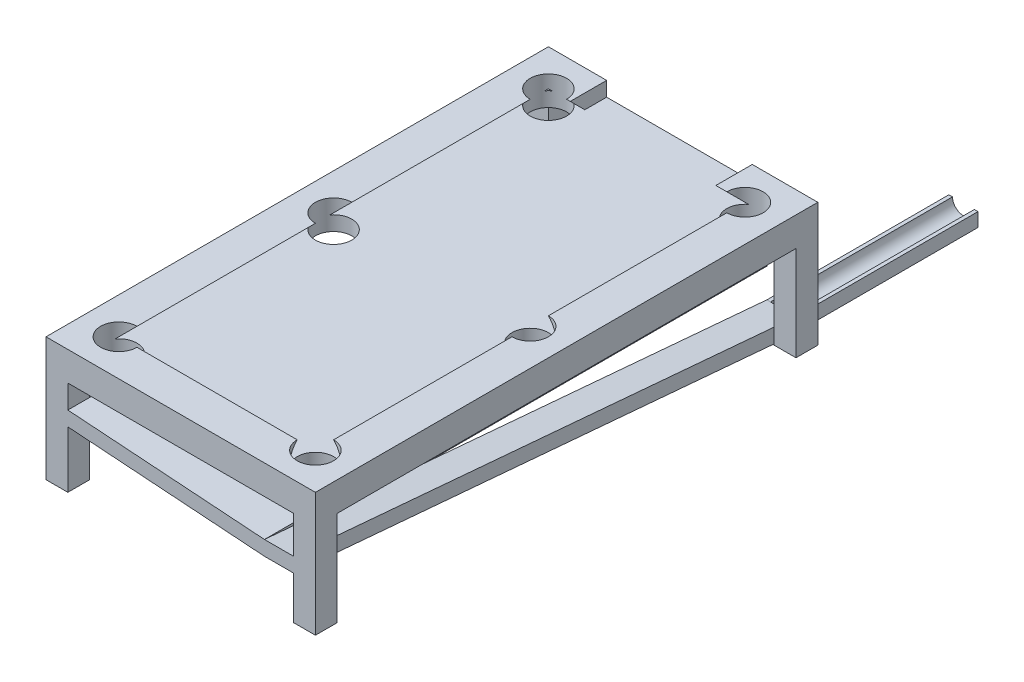
SolidWorks part; units mm, degrees
ref_plane "Front Plane" through (0, 0, 0) normal (0, 0, 1) x (1, 0, 0)
ref_plane "Top Plane" through (0, 0, 0) normal (0, 1, 0) x (1, 0, 0)
ref_plane "Right Plane" through (0, 0, 0) normal (1, 0, 0) x (0, 0, -1)
sketch "Sketch2" plane through (0, 0, 0) normal (0, 1, 0) x (1, 0, 0)
  line L1 (0, 0) -> (370, 0)
  line L2 (0, 0) -> (0, 690)
  line L3 (0, 690) -> (370, 690)
  line L4 (370, 0) -> (370, 690)
  line L5 (50, 50) -> (320, 50)
  line L6 (50, 50) -> (50, 640)
  line L7 (50, 640) -> (320, 640)
  line L8 (320, 50) -> (320, 640)
  dimension "D1" = 690
  dimension "D2" = 370
  dimension "D3" = 590
  dimension "D4" = 270
  dimension "D5" = 50
  dimension "D6" = 50
extrude "Boss-Extrude1" add sketch "Sketch2" along normal blind 20
chamfer "Chamfer1" distance 20 angle 45 4 edges at (185, 0, -640) (320, 0, -345) (185, 0, -50) (50, 0, -345)
ref_plane "Plane1" through (0, 0, -690) normal (0, 0, -1) x (-1, 0, 0)
sketch "Sketch10" plane through (0, 0, 0) normal (0, -1, 0) x (1, 0, 0)
  line L1 (0, 0) -> (370, 0)
  line L2 (0, 0) -> (0, -690)
  line L3 (0, -690) -> (370, -690)
  line L4 (370, 0) -> (370, -690)
extrude "Boss-Extrude6" add sketch "Sketch10" along normal blind 20
sketch "Sketch4" plane through (0, 20, 0) normal (0, 1, 0) x (1, 0, 0)
  line L0 (320, 640) -> (50, 640) construction
  line L1 (50, 640) -> (50, 50) construction
  line L2 (320, 50) -> (320, 640) construction
  circle A0 centre (320, 640) radius 25
  circle A1 centre (50, 640) radius 25
  circle A2 centre (50, 50) radius 25
  circle A3 centre (320, 50) radius 25
  circle A4 centre (320, 345) radius 25
  circle A5 centre (50, 345) radius 25
  line M11 (50, 50) -> (50, 640)
  line M12 (50, 640) -> (320, 640)
  line M13 (320, 640) -> (320, 50)
  line M14 (320, 50) -> (50, 50)
  dimension "D1" = 50
extrude "Cut-Extrude3" cut sketch "Sketch4" against normal through all contours A0 M12 M13 | A0 M13 M12 | A1 M11 M12 | A1 M12 M11 | A5 M11 | A5 M11 | A2 M14 M11 | A2 M11 M14 | A3 M13 M14 | A3 M14 M13 | A4 M13 | A4 M13 | A1 region at (323.5368, 20, -643.5368) region at (309.3897, 20, -629.3897) region at (46.4632, 20, -643.5368) region at (60.6103, 20, -629.3897) region at (309.3897, 20, -345) region at (330.6103, 20, -345) region at (39.3897, 20, -345) region at (60.6103, 20, -345) region at (309.3897, 20, -60.6103) region at (323.5368, 20, -46.4632) region at (46.4632, 20, -46.4632) region at (60.6103, 20, -60.6103)
sketch "Sketch11" plane through (0, -20, 0) normal (0, -1, 0) x (1, 0, 0)
  line L1 (0, 0) -> (30, 0)
  line L2 (0, 0) -> (0, -30)
  line L3 (0, -30) -> (30, -30)
  line L4 (30, 0) -> (30, -30)
  line L5 (370, 0) -> (340, 0)
  line L6 (370, 0) -> (370, -30)
  line L7 (370, -30) -> (340, -30)
  line L8 (340, 0) -> (340, -30)
  line L9 (0, -690) -> (30, -690)
  line L10 (0, -690) -> (0, -660)
  line L11 (0, -660) -> (30, -660)
  line L12 (30, -690) -> (30, -660)
  line L13 (370, -690) -> (340, -690)
  line L14 (370, -690) -> (370, -660)
  line L15 (370, -660) -> (340, -660)
  line L16 (340, -690) -> (340, -660)
  dimension "D1" = 30
extrude "Boss-Extrude7" add sketch "Sketch11" along normal blind 130
sketch "Sketch13" plane through (0, 20, 0) normal (0, 1, 0) x (1, 0, 0)
  line L0 (22, 690) -> (-22, 690) construction
  line L1 (80, 690) -> (280, 690)
  line L2 (80, 690) -> (80, 640)
  line L3 (80, 640) -> (280, 640)
  line L4 (280, 690) -> (280, 640)
  line L5 (295, 640) -> (75, 640) construction
  line L6 (0, 690) -> (0, 0) construction
  dimension "D1" = 200
  dimension "D2" = 80
extrude "Cut-Extrude4" cut sketch "Sketch13" against normal blind 20
sketch "Sketch14" plane through (0, 0, 0) normal (0, 0, 1) x (1, 0, 0)
  line L1 (30, -52.1063) -> (300, -71.0631)
  line L2 (30, -150) -> (30, -20) construction
  line L6 (300, -91.0631) -> (30, -72.1063)
  line L9 (300, -71.0631) -> (300, -91.0631)
  line L10 (30, -52.1063) -> (30, -72.1063)
extrude "Boss-Extrude11" add sketch "Sketch14" against normal blind 690
sketch "Sketch19" plane through (300, 0, 0) normal (1, 0, 0) x (0, 0, -1)
  line L1 (0, -71.0631) -> (690, -131.0631)
  line L2 (0, -91.0631) -> (690, -151.0631)
  line L3 (690, -151.0631) -> (690, -131.0631)
  line L11 (0, -71.0631) -> (0, -91.0631)
  line L12 (0, -91.0631) -> (690, -91.0631)
  line L13 (690, -91.0631) -> (690, -71.0631)
  line L14 (690, -71.0631) -> (0, -71.0631)
  line L15 (0, -71.0631) -> (0, -91.0631)
  dimension "D1" = 0
  dimension "D2" = 20
extrude "Boss-Extrude15" add sketch "Sketch19" along normal blind 40
sketch "Sketch21" plane through (0, -150, 0) normal (0, -1, 0) x (1, 0, 0)
  line L1 (371.7916, -651.7764) -> (372.2206, -651.7764)
  line L2 (371.7916, -651.7764) -> (371.7916, -651.7178)
  line L3 (371.7916, -651.7178) -> (372.2206, -651.7178)
  line L4 (372.2206, -651.7764) -> (372.2206, -651.7178)
  line L5 (369.3993, -651.7471) -> (294.1873, -651.7471)
  line L6 (369.3993, -651.7471) -> (369.3993, -696.7907)
  line L7 (369.3993, -696.7907) -> (294.1873, -696.7907)
  line L8 (294.1873, -651.7471) -> (294.1873, -696.7907)
extrude "Cut-Extrude6" cut sketch "Sketch21" along normal blind 17
sketch "Sketch22" plane through (0, 0, -690) normal (0, 0, -1) x (-1, 0, 0)
  line L4 (-340, -131.0631) -> (-300, -131.0631) construction
  line L9 (-305, -131.0631) -> (-300, -131.0631)
  line L10 (-300, -131.0631) -> (-300, -150)
  line L11 (-335, -131.0631) -> (-340, -131.0631)
  line L16 (-340, -131.0631) -> (-340, -150)
  line L17 (-340, -150) -> (-300, -150)
  arc A0 (-335, -131.0631) -> (-305, -131.0631) centre (-320, -131.0631) ccw
  point P0 (0, 0)
  dimension "D1" = 5
  dimension "D2" = 5
extrude "Boss-Extrude16" add sketch "Sketch22" along normal blind 250
sketch "Sketch24" plane through (300, 0, 0) normal (-1, 0, 0) x (0, 0, 1)
  line L0 (-690, -131.0631) -> (-690, -91.0631)
  line L1 (-690, -91.0631) -> (-230, -91.0631)
  line L2 (-230, -91.0631) -> (-230, -111.0631)
  line L3 (0, -91.0631) -> (-677.7749, -150) construction
  line L5 (-677.7749, -150) -> (-690, -131.0631)
  line L6 (-677.7749, -150) -> (-230, -150)
  line L7 (-230, -150) -> (-230, -111.0631)
